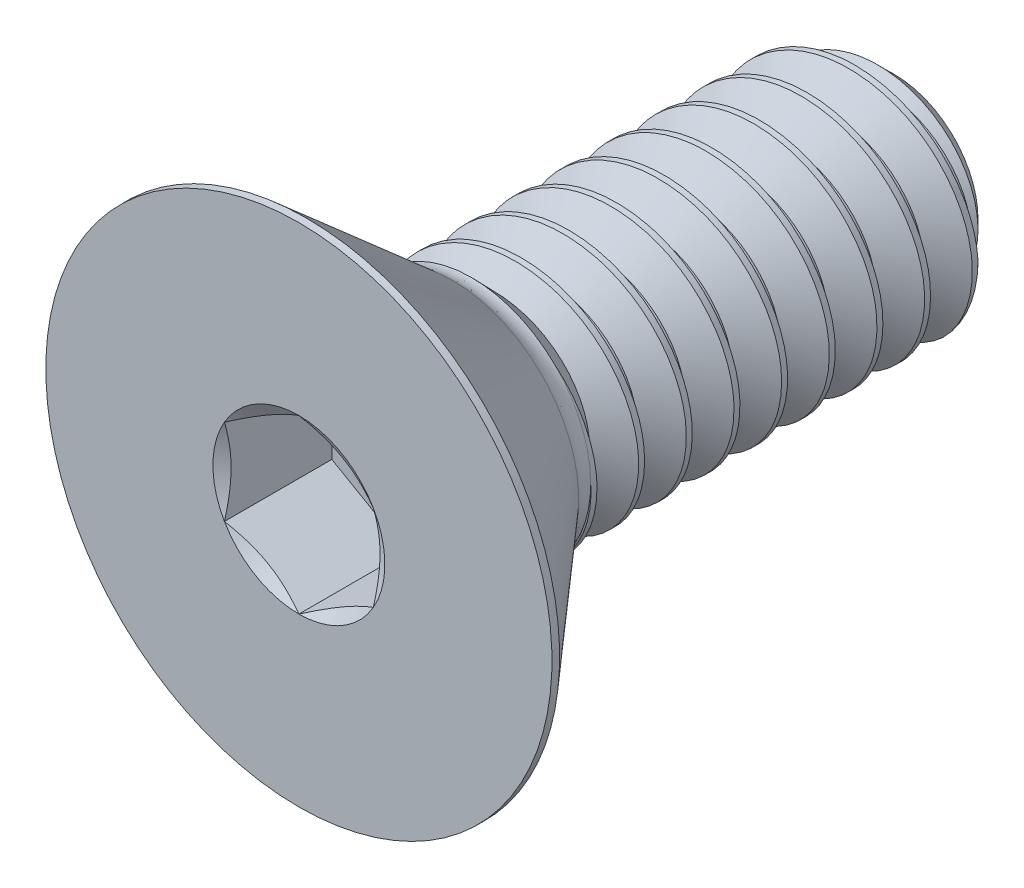
SolidWorks part; units mm, degrees
ref_plane "Front" through (0, 0, 0) normal (0, 0, 1) x (1, 0, 0)
ref_plane "Top" through (0, 0, 0) normal (0, 1, 0) x (1, 0, 0)
ref_plane "Right" through (0, 0, 0) normal (1, 0, 0) x (0, 0, -1)
sketch "Sketch1" plane through (0, 0, 0) normal (1, 0, 0) x (0, 0, -1)
  line L0 (0, 6.7437) -> (0.2045, 6.7437) construction
  line L1 (0.2045, 6.7437) -> (4.0894, 3.3666) construction
  line L2 (0, 3.175) -> (15.875, 3.175)
  line L3 (15.875, 3.175) -> (15.875, 0)
  line L4 (15.875, 0) -> (0, 0)
  line L5 (0, 0) -> (0, 6.7437) construction
  line L6 (0, 6.7437) -> (0, -6.7437) construction
  line L7 (15.875, 3.175) -> (15.875, -3.175) construction
  line L8 (0, -6.7437) -> (0.2045, -6.7437) construction
  line L9 (0.2045, -6.7437) -> (4.0894, -3.3666) construction
  line L11 (0, 3.175) -> (0, 0)
  line L12 (4.6018, 3.175) -> (4.6018, 0) construction
  line L13 (-9.525, 0) -> (-9.525, 3.175) construction
  arc A1 (4.0894, 3.3666) -> (4.6018, 3.175) centre (4.6018, 3.956) ccw construction
  dimension "D1" = 0.2045
  dimension "Min Thread" = 25.4
revolve "Revolve1" add sketch "Sketch1" angle 360 mid plane about L4
sketch "Sketch3" plane through (0, 0, -15.875) normal (0, 0, -1) x (-1, 0, 0)
  circle A0 centre (0, 0) radius 3.175
curve "Helix/Spiral1" pitch 1.27 height 15.875 radius 3.175 centre (0, 0, -15.875) axis (0, 0, 1) start towards (0, 1, 0)
sketch "Sketch2" plane through (0, 0, 0) normal (1, 0, 0) x (0, 0, -1)
  line L0 (15.875, 3.175) -> (16.9863, 3.175)
  line L1 (16.9863, 3.175) -> (16.51, 2.3501)
  line L2 (16.51, 2.3501) -> (16.3513, 2.3501)
  line L3 (16.3513, 2.3501) -> (15.875, 3.175)
  line L4 (16.1131, 2.7626) -> (16.7481, 2.7626) construction
  dimension "D1" = 60
  dimension "D2" = 0.1588
  dimension "D3" = 0.635
ref_plane "Plane2" through (0, 0, 9.525) normal (0, 0, 1) x (1, 0, 0)
chamfer "Chamfer1" distance 0.9525 angle 45 1 edges at (0, 3.175, -15.875)
sweep "Cut-Sweep1" cut profiles "Sketch2" path "Helix/Spiral1" align with end faces yes
sketch "Sketch7" plane through (0, 0, 0) normal (1, 0, 0) x (0, 0, -1)
  line L0 (0, 6.7437) -> (0.2045, 6.7437) construction
  line L1 (0.2045, 6.7437) -> (4.0894, 3.3666) construction
  line L2 (0, 6.7437) -> (0.2045, 6.7437)
  line L3 (0.2045, 6.7437) -> (4.0894, 3.3666)
  line L4 (4.6018, 3.175) -> (4.6018, 0) construction
  line L5 (4.6018, 3.175) -> (4.6018, 0)
  line L7 (0, 0) -> (0, 6.7437) construction
  line L8 (0, 0) -> (0, 6.7437)
  line L9 (0, 0) -> (4.6018, 0)
  line L10 (5.7417, 0) -> (-5.7417, 0) construction
  arc A0 (4.0894, 3.3666) -> (4.6018, 3.175) centre (4.6018, 3.956) ccw construction
  arc A1 (4.0894, 3.3666) -> (4.6018, 3.175) centre (4.6018, 3.956) ccw
revolve "Revolve2" add sketch "Sketch7" angle 360 mid plane about L9
ref_plane "Plane1" through (0, 0, -4.6018) normal (0, 0, 1) x (1, 0, 0)
sketch "Sketch8" plane through (0, 0, -4.6018) normal (0, 0, 1) x (1, 0, 0)
  circle A0 centre (0, 0) radius 3.175
extrude "Boss-Extrude1" add sketch "Sketch8" against normal through all draft 46
sketch "Sketch5" plane through (0, 0, 0) normal (0, 0, 1) x (1, 0, 0)
  line L0 (0, 0) -> (-2.2914, 0) construction
  line L1 (0, 0) -> (-2.7496, 1.5875) construction
  line L2 (0, 0) -> (-2.7496, -1.5875) construction
  line L6 (0, 2.2914) -> (0, 1.8898) construction
  line L7 (0, 1.8898) -> (0, 1.4883) construction
  line L9 (0, 2.2914) -> (-1.9844, 1.1457)
  line L10 (-1.9844, 1.1457) -> (-1.9844, -1.1457)
  line L11 (-1.9844, -1.1457) -> (0, -2.2914)
  line L12 (0, -2.2914) -> (1.9844, -1.1457)
  line L13 (1.9844, -1.1457) -> (1.9844, 1.1457)
  line L14 (1.9844, 1.1457) -> (0, 2.2914)
  circle A0 centre (0, 0) radius 2.2914 construction
  circle A1 centre (0, 0) radius 1.8898 construction
  circle A2 centre (0, 0) radius 1.4883 construction
  circle A3 centre (0, 0) radius 1.9844 construction
  dimension "D3" = 2.9766
  dimension "D4" = 30
  dimension "D5" = 30
  dimension "Hex" = 3.9688
extrude "Cut-Extrude2" cut sketch "Sketch5" against normal blind 2.8626
sketch "Sketch6" plane through (0, 0, 0) normal (0, 0, 1) x (1, 0, 0)
  circle A0 centre (0, 0) radius 2.2914
extrude "Cut-Extrude3" cut sketch "Sketch6" against normal blind 2.8626 draft 60
sketch "Sketch9" [suppressed] plane through (0, 0, -3.6076) normal (0, 0, 1) x (1, 0, 0)
  circle A1 centre (0, 0) radius 2.413
  circle A2 centre (0, 0) radius 2.413
  point P0 (0, 2.413)
  dimension "D1" = 0
extrude "Boss-Extrude2" [suppressed] add sketch "Sketch9" against normal up to surface (15.4424 mm away) up to plane "Plane2"
sketch "Sketch10" plane through (0, 0, 0) normal (1, 0, 0) x (0, 0, -1)
  line L0 (15.875, 3.175) -> (15.875, -3.175) construction
  point P0 (13.97, -3.175)
  dimension "D1" = 1.905
equation "\"D3@Helix/Spiral1\" = \"Lg@Sketch1\""
equation "\"D2@Sketch2\" = \"D4@Helix/Spiral1\" * .125"
equation "\"D3@Sketch2\" = \"D4@Helix/Spiral1\" * .5"
equation "\"D1@Chamfer1\" = \"D4@Helix/Spiral1\" * .75"
equation "\"D1@Cut-Extrude2\" = \"Head Ht@Sketch1\" * .7"
equation "\"D1@Sketch1\" = \"Head Ht@Sketch1\" * .05"
equation "\"D1@Sketch10\" = \"D4@Helix/Spiral1\" * 1.5"
equation "\"D1@Cut-Extrude3\" = \"D1@Cut-Extrude2\""
equation "\"D3@Sketch5\" = \"Hex@Sketch5\" * .75"
